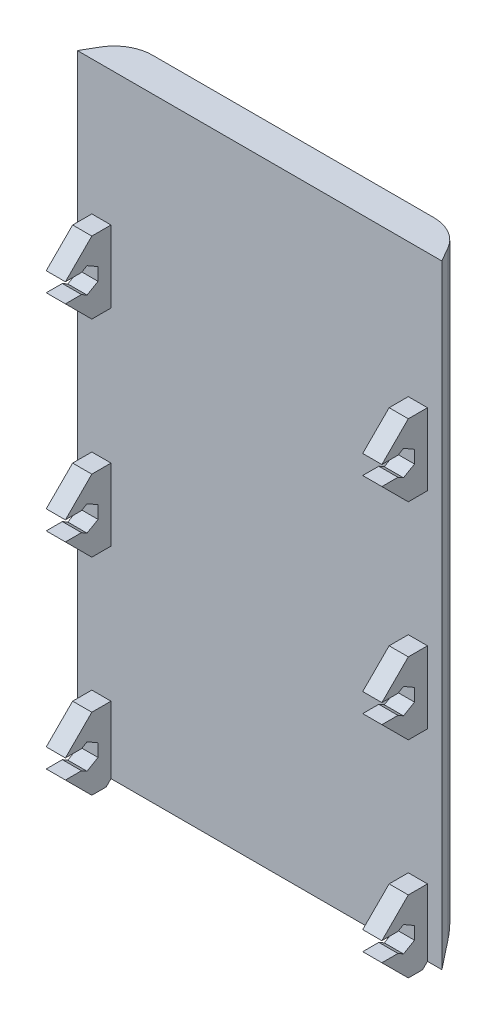
SolidWorks part; units mm, degrees
ref_plane "Front Plane" through (0, 0, 0) normal (0, 0, 1) x (1, 0, 0)
ref_plane "Top Plane" through (0, 0, 0) normal (0, 1, 0) x (1, 0, 0)
ref_plane "Right Plane" through (0, 0, 0) normal (1, 0, 0) x (0, 0, -1)
sketch "Sketch1" plane through (0, 0, 0) normal (0, 1, 0) x (1, 0, 0)
  line L0 (-9.2151, 0) -> (-9.2151, -10)
  line L1 (-9.2151, -10) -> (-5.2151, -10)
  line L2 (-5.2151, -10) -> (-5.2151, 0)
  line L3 (-5.2151, 0) -> (56.7849, 0)
  line L4 (56.7849, 0) -> (56.7849, -10)
  line L5 (56.7849, -10) -> (60.7849, -10)
  line L6 (60.7849, -10) -> (60.7849, 0)
  line L7 (60.7849, 0) -> (63.7849, 0)
  line L8 (-9.2151, 0) -> (-12.2151, 0)
  line L9 (-12.2151, 0) -> (-8.1737, 7)
  line L10 (-8.1737, 7) -> (59.7434, 7)
  line L11 (59.7434, 7) -> (63.7849, 0)
  line L12 (25.7849, 7) -> (25.7849, 0) construction
  dimension "D1" = 3
  dimension "D2" = 10
  dimension "D3" = 70
  dimension "D4" = 7
  dimension "D5" = 4
  dimension "D6" = 60
extrude "Boss-Extrude1" add sketch "Sketch1" along normal blind 129
sketch "Sketch4" plane through (60.7849, 0, 0) normal (1, 0, 0) x (0, 0, -1)
  line L0 (0, 129) -> (0, 0) construction
  line L1 (-37.5185, 129) -> (0, 129)
  line L2 (-37.5185, 129) -> (-37.5185, 101)
  line L3 (-37.5185, 101) -> (0, 101)
  line L4 (0, 129) -> (0, 101)
  line L5 (-37.5185, 129) -> (0, 101) construction
  line L6 (-37.5185, 101) -> (0, 129) construction
  line L7 (-10, 129) -> (0, 129) construction
  point P0 (-18.7592, 115)
  dimension "D1" = 28
extrude "Cut-Extrude1" cut sketch "Sketch4" against normal through all
sketch "Sketch5" plane through (60.7849, 0, 0) normal (1, 0, 0) x (0, 0, -1)
  line L0 (0, 129) -> (0, 0) construction
  line L1 (-33.3149, 86) -> (0, 86)
  line L2 (-33.3149, 86) -> (-33.3149, 58)
  line L3 (-33.3149, 58) -> (0, 58)
  line L4 (0, 86) -> (0, 58)
  line L5 (-33.3149, 86) -> (0, 58) construction
  line L6 (-33.3149, 58) -> (0, 86) construction
  line L7 (-10, 101) -> (0, 101) construction
  point P0 (-16.6574, 72)
  dimension "D1" = 28
  dimension "D2" = 15
extrude "Cut-Extrude2" cut sketch "Sketch5" against normal through all
sketch "Sketch6" plane through (0, 0, 0) normal (1, 0, 0) x (0, 0, -1)
  line L0 (-10, 101) -> (-10, 86) construction
  line L1 (-2.7, 94.8279) -> (-5, 96.1558)
  line L2 (-5, 96.1558) -> (-7.3, 94.8279)
  line L3 (-7.3, 94.8279) -> (-7.3, 92.1721)
  line L4 (-7.3, 92.1721) -> (-5, 90.8442)
  line L5 (-5, 90.8442) -> (-2.7, 92.1721)
  line L6 (-2.7, 92.1721) -> (-2.7, 94.8279)
  line L7 (-10, 101) -> (0, 101) construction
  line L8 (-6.15, 95.4919) -> (-10, 95.4919)
  line L9 (-6.15, 91.5081) -> (-10, 91.5081)
  line L10 (-10, 91.5081) -> (-10, 95.4919)
  circle A1 centre (-5, 93.5) radius 2.3 construction
  dimension "D1" = 4.6
  dimension "D2" = 7.5
  dimension "D3" = 5
extrude "Cut-Extrude3" cut sketch "Sketch6" against normal through all and the other way through all contours L10 L9 L4 L3 L2 L8 | L5 L6 L1 L2 L3 L4 region at (0, 93.5, 5) region at (0, 93.5, 8.5351)
pattern_linear "LPattern1" count 4 spacing 43 along (0, -1, 0) of "Cut-Extrude2", "Cut-Extrude3"
chamfer "Chamfer6" distance 8 angle 45 1 edges at (25.7849, 0, -7)
fillet "Fillet1" radius 8 2 edges at (-8.1737, 68.5, -7) (59.7434, 68.5, -7)
chamfer "Chamfer5" distance 6 angle 45 12 edges at (58.7849, 101, 10) (58.7849, 86, 10) (-7.2151, 101, 10) (-7.2151, 86, 10) (-7.2151, 58, 10) (-7.2151, 43, 10) (58.7849, 58, 10) (58.7849, 43, 10) (58.7849, 15, 10) (58.7849, 0, 10) (-7.2151, 0, 10) (-7.2151, 15, 10)
